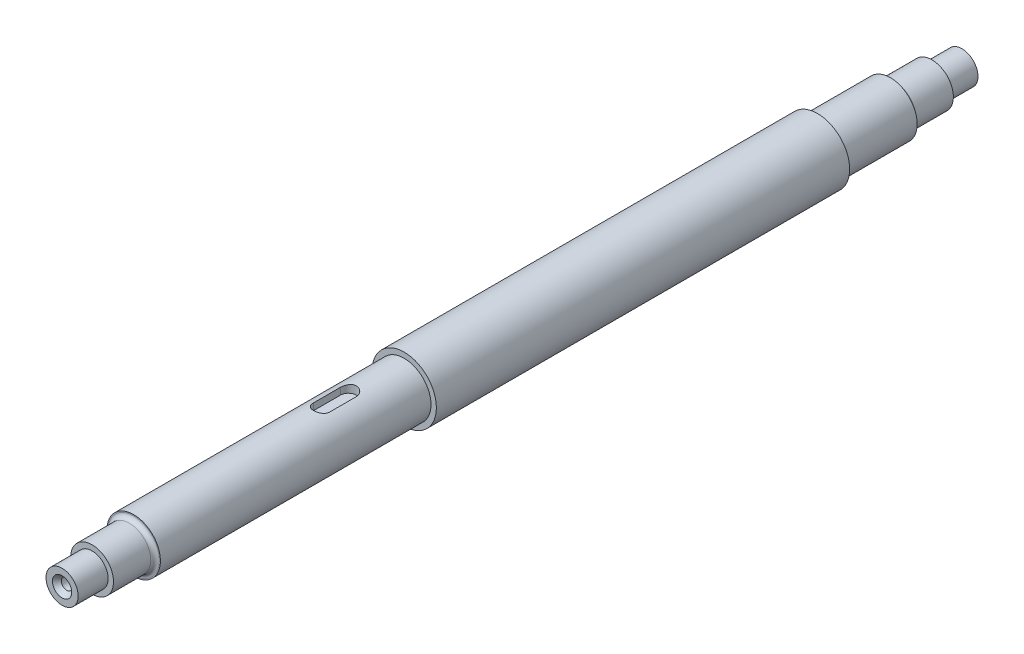
SolidWorks part; units mm, degrees
material "Alloy Steel"
ref_plane "Front Plane" through (0, 0, 0) normal (0, 0, 1) x (1, 0, 0)
ref_plane "Top Plane" through (0, 0, 0) normal (0, 1, 0) x (1, 0, 0)
ref_plane "Right Plane" through (0, 0, 0) normal (1, 0, 0) x (0, 0, -1)
sketch "Sketch1" plane through (0, 0, 0) normal (0, 0, 1) x (1, 0, 0)
  circle A0 centre (0, 0) radius 9.525
  dimension "D1" = 19.05
extrude "Boss-Extrude1" add sketch "Sketch1" along normal mid plane 279.4
ref_plane "Plane1" through (0, 0, 90.551) normal (0, 0, 1) x (1, 0, 0)
sketch "Sketch3" plane through (0, 0, 90.551) normal (0, 0, 1) x (1, 0, 0)
  circle A0 centre (0, 0) radius 7.9375
  circle A1 centre (0, 0) radius 9.525
  circle A2 centre (0, 0) radius 9.525
  dimension "D2" = 15.875
  dimension "D1" = 0
extrude "Cut-Extrude1" cut sketch "Sketch3" along normal up to next
mirror "Mirror1" about plane through (0, 0, 0) normal (0, 0, 1) of "Cut-Extrude1"
ref_plane "Plane2" through (0, 0, 124.46) normal (0, 0, 1) x (1, 0, 0)
sketch "Sketch4" plane through (0, 0, 124.46) normal (0, 0, 1) x (1, 0, 0)
  circle A0 centre (0, 0) radius 4.7625
  circle A1 centre (0, 0) radius 7.9375
  circle A2 centre (0, 0) radius 7.9375
  dimension "D2" = 9.525
  dimension "D1" = 0
extrude "Cut-Extrude2" cut sketch "Sketch4" along normal up to next
mirror "Mirror2" about plane through (0, 0, 0) normal (0, 0, 1) of "Cut-Extrude2"
sketch "Sketch5" plane through (0, 0, 90.551) normal (0, 0, 1) x (1, 0, 0)
  circle A0 centre (0, 0) radius 9.525 construction
  circle A1 centre (0, 0) radius 9.525
  circle A3 centre (0, 0) radius 7.9375 construction
  circle A4 centre (0, 0) radius 7.9375
extrude "Cut-Extrude3" cut sketch "Sketch5" against normal blind 58.6105
ref_plane "Plane3" through (0, 7.9375, 0) normal (0, 1, 0) x (1, 0, 0)
sketch "Sketch6" plane through (0, 7.9375, 0) normal (0, 1, 0) x (1, 0, 0)
  line L0 (-9.525, -31.9405) -> (9.525, -31.9405) construction
  line L2 (-9.525, -31.9405) -> (9.525, -31.9405)
  line L3 (-7.9375, -124.46) -> (7.9375, -124.46) construction
  line L4 (0, -90.551) -> (0, -31.9405) construction
  line L8 (0, -56.4197) -> (0, -48.4822) construction
  line L9 (-2.3812, -56.4197) -> (-2.3813, -48.4822)
  line L10 (2.3813, -56.4197) -> (2.3812, -48.4822)
  line L11 (0, -46.101) -> (-5.2744, -46.101) construction
  line L12 (0, -58.801) -> (-5.6689, -58.801) construction
  line L13 (-7.9375, -124.46) -> (7.9375, -124.46) construction
  arc A0 (-2.3812, -56.4197) -> (2.3813, -56.4197) centre (0, -56.4197) ccw
  arc A1 (2.3812, -48.4822) -> (-2.3813, -48.4822) centre (0, -48.4822) ccw
  point P14 (0, -52.451)
  point P23 (0, -90.551)
  dimension "D1" = 4.7625
  dimension "D2" = 12.7
  dimension "D3" = 38.1
  dimension "D4" = 33.909
extrude "Cut-Extrude4" cut sketch "Sketch6" against normal blind 2.3812 contours L10 A1 L9 A0 region at (0, 7.9375, 52.451)
sketch "Sketch7" plane through (0, 0, 124.46) normal (0, 0, 1) x (1, 0, 0)
  circle A0 centre (0, 0) radius 7.9375 construction
  circle A1 centre (0, 0) radius 7.9375
  circle A2 centre (0, 0) radius 6.35
  dimension "D1" = 12.7
extrude "Cut-Extrude5" cut sketch "Sketch7" against normal blind 12.319
fillet "Fillet1" radius 1.27 1 edges at (6.35, 0, 112.141)
sketch "Sketch8" plane through (0, 0, 139.7) normal (0, 0, 1) x (1, 0, 0)
  circle A0 centre (0, 0) radius 4.7625 construction
  circle A1 centre (0, 0) radius 4.7625
extrude "Cut-Extrude6" cut sketch "Sketch8" against normal blind 6.35
sketch "Sketch9" plane through (0, 0, 133.35) normal (0, 0, 1) x (1, 0, 0)
  circle A0 centre (0, 0) radius 4.7625 construction
  circle A1 centre (0, 0) radius 4.7625
  point P4 (0, 0)
hole_wizard "CSK for #4 Flat Head Machine Screw1" positions "3DSketch1" profile "Sketch10" countersink size "#4" standard "ANSI Inch"
sketch3d "3DSketch1"
  point P0 (0, 0, 133.35)
sketch "Sketch10" plane through (0, 0, 133.35) normal (1, 0, 0) x (0, -1, 0)
  line L0 (0, 0) -> (0, 7.3306)
  line L1 (0, 7.3306) -> (1.6319, 6.35)
  line L2 (1.6319, 6.35) -> (1.6319, 1.4098)
  line L3 (1.6319, 1.4098) -> (2.8575, 0)
  line L5 (2.8575, 0) -> (0, 0)
  line L6 (-1.6319, 1.4098) -> (-2.8575, 0) construction
  line L10 (0, 7.3306) -> (-1.6319, 6.35) construction
  line L11 (0, -6.35) -> (0, 107.95) construction
  dimension "Hole Dia." = 3.2639
  dimension "Hole Depth" = 6.35
  dimension "Near C'Sink Dia." = 5.715
  dimension "Near C'Sink Angle" = 82
  dimension "Drill Angle" = 118
mirror "Mirror3" about plane through (0, 0, 0) normal (0, 0, 1) of "CSK for #4 Flat Head Machine Screw1", "Fillet1", "Cut-Extrude5", "Cut-Extrude6"
